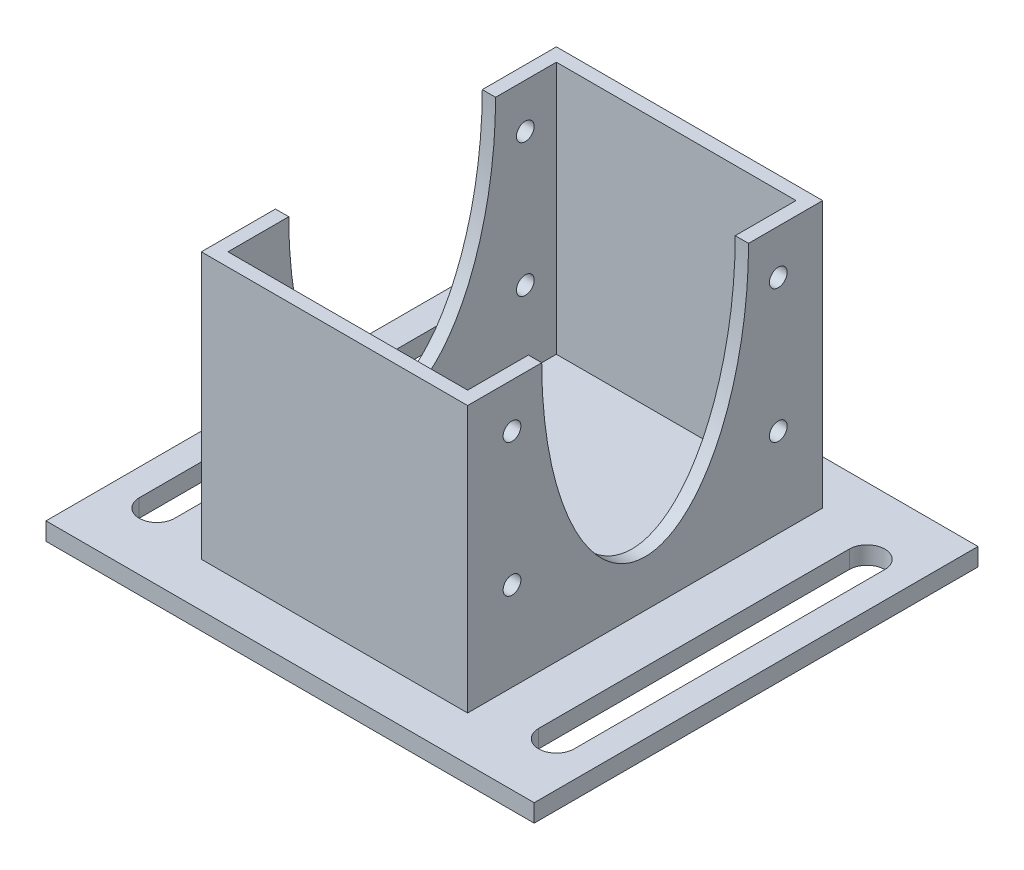
SolidWorks part; units mm, degrees
ref_plane "Front Plane" through (0, 0, 0) normal (0, 0, 1) x (1, 0, 0)
ref_plane "Top Plane" through (0, 0, 0) normal (0, 1, 0) x (1, 0, 0)
ref_plane "Right Plane" through (0, 0, 0) normal (1, 0, 0) x (0, 0, -1)
sketch "Sketch1" plane through (0, 0, 0) normal (0, 1, 0) x (1, 0, 0)
  line L1 (-38.1, 50.8) -> (38.1, 50.8)
  line L2 (-38.1, 50.8) -> (-38.1, -50.8)
  line L3 (-38.1, -50.8) -> (38.1, -50.8)
  line L4 (38.1, 50.8) -> (38.1, -50.8)
  line L5 (-38.1, 50.8) -> (38.1, -50.8) construction
  line L6 (-38.1, -50.8) -> (38.1, 50.8) construction
  point P0 (0, 0)
  dimension "D1" = 101.6
  dimension "D2" = 76.2
extrude "Boss-Extrude1" add sketch "Sketch1" along normal blind 76.2 contours L2 L3 L4 L1
sketch "Sketch2" plane through (-38.1, 0, 0) normal (-1, 0, 0) x (0, 0, 1)
  line L0 (0, 76.2) -> (0, 0) construction
  line L1 (-50.8, 76.2) -> (50.8, 76.2) construction
  ellipse E0 centre (0, 76.2) end of major axis (0, 13.326) minor radius 29.5918
extrude "Cut-Extrude1" cut sketch "Sketch2" against normal through all
shell "Shell1" thickness 3.81 removed face at (0, 76.2, 40.1959) removed face at (0, 44.763, 0) removed face at (0, 76.2, -40.1959)
sketch "Sketch4" plane through (-38.1, 0, 0) normal (-1, 0, 0) x (0, 0, 1)
  line L0 (0, 0) -> (0, 86.768) construction
  line L1 (-50.8, 63.5) -> (50.8, 63.5) construction
  line L4 (-50.8, 0) -> (50.8, 0) construction
  line L5 (-50.8, 0) -> (50.8, 0) construction
  line L6 (-50.8, 25.4) -> (50.8, 25.4) construction
  line L7 (-50.8, 76.2) -> (-50.8, 0) construction
  line L8 (50.8, 76.2) -> (50.8, 0) construction
  line L9 (-38.1, 76.2) -> (-38.1, 0) construction
  circle A0 centre (-38.1, 63.5) radius 2.54
  circle A1 centre (-38.1, 25.4) radius 2.54
  circle A2 centre (38.1, 25.4) radius 2.54
  circle A3 centre (38.1, 63.5) radius 2.54
  dimension "D4" = 5.08
  dimension "D1" = 63.5
  dimension "D2" = 25.4
  dimension "D3" = 12.7
extrude "Cut-Extrude2" cut sketch "Sketch4" against normal through all
sketch "Sketch5" plane through (0, 0, 0) normal (0, -1, 0) x (1, 0, 0)
  line L1 (-69.85, 63.5) -> (69.85, 63.5)
  line L2 (-69.85, 63.5) -> (-69.85, -63.5)
  line L3 (-69.85, -63.5) -> (69.85, -63.5)
  line L4 (69.85, 63.5) -> (69.85, -63.5)
  line L5 (-69.85, 63.5) -> (69.85, -63.5) construction
  line L6 (-69.85, -63.5) -> (69.85, 63.5) construction
  point P0 (0, 0)
  dimension "D1" = 127
  dimension "D2" = 139.7
extrude "Boss-Extrude2" add sketch "Sketch5" along normal blind 5.08
sketch "Sketch6" plane through (0, 0, 0) normal (0, 1, 0) x (1, 0, 0)
  line L0 (0, 63.5) -> (0, -63.5) construction
  line L1 (-69.85, 63.5) -> (69.85, 63.5) construction
  line L2 (69.85, -63.5) -> (-69.85, -63.5) construction
  line L3 (-69.85, 0) -> (69.85, 0) construction
  line L4 (-69.85, -63.5) -> (-69.85, 63.5) construction
  line L5 (69.85, 63.5) -> (69.85, -63.5) construction
  line L6 (-57.15, 44.45) -> (-57.15, -44.45) construction
  line L7 (-57.15, 44.45) -> (-57.15, -44.45) construction
  line L8 (-52.07, 44.45) -> (-52.07, -44.45)
  line L9 (-62.23, 44.45) -> (-62.23, -44.45)
  line L10 (57.15, 44.45) -> (57.15, -44.45) construction
  line L11 (52.07, 44.45) -> (52.07, -44.45)
  line L12 (62.23, 44.45) -> (62.23, -44.45)
  arc A0 (-52.07, 44.45) -> (-62.23, 44.45) centre (-57.15, 44.45) ccw
  arc A1 (-62.23, -44.45) -> (-52.07, -44.45) centre (-57.15, -44.45) ccw
  arc A2 (52.07, 44.45) -> (62.23, 44.45) centre (57.15, 44.45) cw
  arc A3 (62.23, -44.45) -> (52.07, -44.45) centre (57.15, -44.45) cw
  point P14 (-57.15, 0)
  point P15 (-57.15, 0)
  point P22 (57.15, 0)
  dimension "D2" = 5.08
  dimension "D1" = 88.9
  dimension "D3" = 57.15
extrude "Cut-Extrude3" cut sketch "Sketch6" against normal through all
